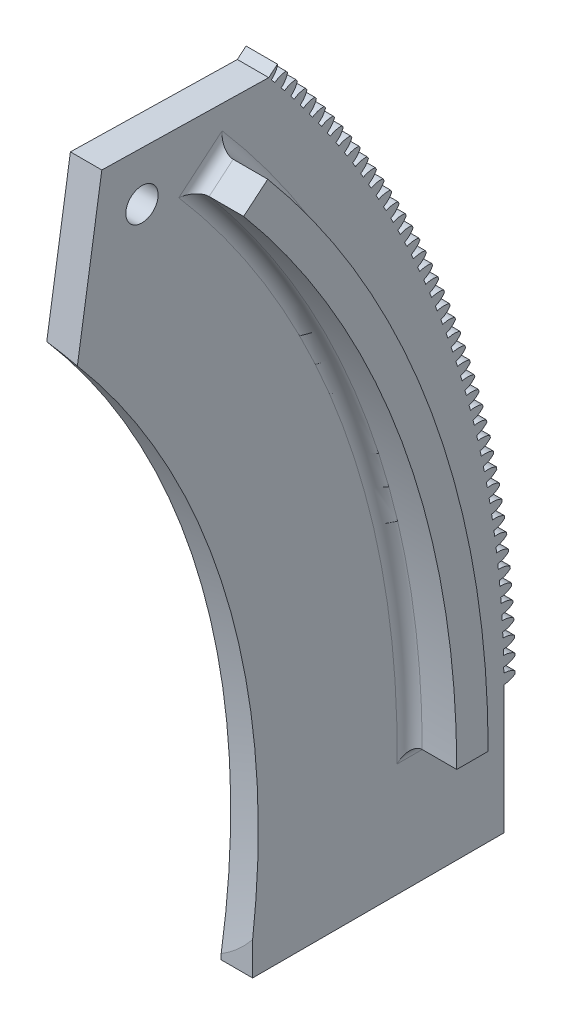
SolidWorks part; units mm, degrees
material "ABS"
ref_plane "Front Plane" through (0, 0, 0) normal (0, 0, 1) x (1, 0, 0)
ref_plane "Top Plane" through (0, 0, 0) normal (0, 1, 0) x (1, 0, 0)
ref_plane "Right Plane" through (0, 0, 0) normal (1, 0, 0) x (0, 0, -1)
ref_plane "Plane2" through (6.35, 0, 0) normal (1, 0, 0) x (0, 0, -1)
sketch "Sketch1" plane through (0, 0, 0) normal (1, 0, 0) x (0, 0, -1)
  line L0 (-1000, 0) -> (152.4, 0) construction
  line L1 (152.4, 0) -> (152.4, -25.4)
  line L2 (0, 0) -> (116.7452, 97.9608) construction
  line L4 (203.2, 0) -> (49000, 0) construction
  line L7 (152.4, -25.4) -> (203.2, -25.4)
  line L8 (203.2, 0) -> (203.2, -25.4)
  line L10 (-19.9245, -15.6845) -> (159.6649, 125.6875) construction
  line L61 (160.8976, 124.1056) -> (0, 0) construction
  line L62 (136.2027, 114.2876) -> (121.9167, 131.313) construction
  line L63 (116.7452, 97.9608) -> (121.9167, 131.313)
  line L67 (121.9167, 131.313) -> (155.6602, 130.6144)
  line L68 (0, 0) -> (35966.99, 34732.9185) construction
  line L69 (159.6736, 125.6943) -> (159.6985, 125.714) construction
  arc A2 (152.4, 0) -> (116.7452, 97.9608) centre (0, 0) ccw
  circle A19 centre (0, 0) radius 203.2 construction
  arc A22 (155.6602, 130.6144) -> (203.2, 0) centre (0, 0) cw
  point P6 (159.6985, 125.714)
  point P7 (116.7452, 97.9608)
  dimension "D1" = 152.4
  dimension "D2" = 6.35
  dimension "D12" = 406.4
  dimension "D3" = 40
  dimension "D4" = 50.8
  dimension "D5" = 25.4
  dimension "D11" = 22.225
  dimension "D13" = 44
sketch "Sketch2" plane through (6.35, 0, 0) normal (1, 0, 0) x (0, 0, -1)
  line L0 (0, 0) -> (165.1, 0) construction
  line L1 (165.1, 0) -> (190.5, 0) construction
  line L2 (0, 0) -> (49240.3877, 8682.4089) construction
  circle A0 centre (165.1, 0) radius 3.2639
  circle A1 centre (190.5, 0) radius 3.2639
  arc A3 (165.1, 0) -> (162.5918, 28.6693) centre (0, 0) ccw construction
  circle A4 centre (162.5918, 28.6693) radius 3.2639
  arc A5 (190.5, 0) -> (187.6059, 33.08) centre (0, 0) ccw construction
  circle A6 centre (187.6059, 33.08) radius 3.2639
  dimension "D3" = 6.5278
  dimension "D4" = 6.5278
  dimension "D6" = 6.5278
  dimension "D7" = 6.5278
  dimension "D1" = 165.1
  dimension "D2" = 25.4
  dimension "D5" = 10
sketch "Sketch11" plane through (6.35, 0, 0) normal (1, 0, 0) x (0, 0, -1)
  line L0 (-785.502, -659.1144) -> (0, 0) construction
  line L2 (-1000, 0) -> (0, 0) construction
  line L3 (203.2, 0) -> (205.5, 0)
  line L4 (155.6602, 130.6144) -> (157.4221, 132.0929)
  line L5 (157.4221, 132.0929) -> (921.7047, 773.4021) construction
  arc A0 (-230, 0) -> (-176.1902, -147.8412) centre (0, 0) ccw construction
  arc A1 (-205.5, 0) -> (-157.4221, -132.0929) centre (0, 0) ccw construction
  arc A2 (-203.1, 0) -> (-155.5836, -130.5502) centre (0, 0) ccw construction
  arc A3 (205.5, 0) -> (157.4221, 132.0929) centre (0, 0) ccw
  arc A4 (230, 0) -> (176.1902, 147.8412) centre (0, 0) ccw construction
  arc A5 (-203.1, 0) -> (-155.5836, -130.5502) centre (0, 0) ccw
  arc A6 (155.6602, 130.6144) -> (203.2, 0) centre (0, 0) cw
  dimension "D1" = 460
  dimension "D2" = 411
  dimension "D4" = 203.2
  dimension "D3" = 2.4
  dimension "D5" = 40
extrude "Boss-Extrude2" add sketch "Sketch11" against normal blind 6.35 contours L3 A3 L4 region at (6.35, 69.9814, -192.2722)
sketch "Sketch12" plane through (6.35, 0, 0) normal (1, 0, 0) x (0, 0, -1)
  line L0 (0, 0) -> (205.5, 0) construction
  line L1 (203.2, 0) -> (205.5, 0) construction
  line L2 (204.4985, 0.7854) -> (204.4985, -0.7854) construction
  line L3 (0, 0) -> (203.1992, 0.5545) construction
  line L4 (202.3406, 0) -> (206.4945, 1.5119) construction
  line L5 (0, 0) -> (206.4939, 1.5861) construction
  line L6 (204.4985, 0.7854) -> (204.4864, 2.3561) construction
  circle A0 centre (0, 0) radius 204.5 construction
  arc A1 (205.5, 0) -> (157.4221, 132.0929) centre (0, 0) ccw construction
  circle A2 centre (0, 0) radius 203.2 construction
  arc A3 (203.1992, 0.5545) -> (206.4856, 2.4358) centre (203.1888, 4.3838) ccw
  arc A4 (206.5, 0) -> (206.4856, -2.4358) centre (0, 0) cw
  arc A5 (203.1992, -0.5545) -> (206.4856, -2.4358) centre (203.1888, -4.3838) cw
  arc A6 (206.5, 0) -> (158.1882, 132.7356) centre (0, 0) ccw
  arc A7 (206.5, 0) -> (206.4856, 2.4358) centre (0, 0) ccw
  arc A8 (203.1992, 0.5545) -> (203.1992, -0.5545) centre (0, 0) cw
  dimension "D1" = 409
  dimension "D5" = 406.4
  dimension "D3" = 20
  dimension "D4" = 0.44
  dimension "D2" = 1
extrude "Boss-Extrude3" add sketch "Sketch1" along normal blind 6.35
extrude "Cut-Extrude4" cut sketch "Sketch12" against normal blind 6.35
pattern_circular "CirPattern3" count 100 every 0.88 about axis through (0, 0, 0) along (1, 0, 0) of "Cut-Extrude4"
sketch "Sketch15" plane through (6.35, 0, 0) normal (1, 0, 0) x (0, 0, -1)
  line L0 (0, 0) -> (130.0347, 121.2593) construction
  line L1 (-196961.5506, -34729.6355) -> (246201.9383, 43412.0444) construction
  circle A0 centre (130.0347, 121.2593) radius 3.2639
  dimension "D3" = 6.5278
  dimension "D1" = 177.8
  dimension "D2" = 33
extrude "Cut-Extrude7" cut sketch "Sketch15" against normal through all
sketch "Sketch21" plane through (0, 0, 0) normal (0, 1, 0) x (1, 0, 0)
  line L0 (0, 0) -> (-11.1125, 0) construction
  line L1 (12.7, 0) -> (12.7, 152.4)
  line L2 (0, 0) -> (12.7, 0) construction
  line L3 (-11.1125, 0) -> (-11.1125, 38.1) construction
  line L4 (-11.1125, 38.1) -> (-127.8666, 38.1)
  line L5 (-11.1125, 38.1) -> (105.6416, 38.1)
  line L6 (107.5153, 38.1) -> (-49892.4847, 38.1) construction
  line L7 (-1000, 0) -> (49000, 0) construction
  arc A0 (105.6416, 38.1) -> (-127.8666, 38.1) centre (-11.1125, 38.1) ccw
  dimension "D3" = 12.7
  dimension "D1" = 11.1125
  dimension "D2" = 152.4
  dimension "D4" = 38.1
revolve "Cut-Revolve7" cut sketch "Sketch21" angle 360 about L7 reverse direction yes
sketch "Sketch22" plane through (6.35, 0, 0) normal (1, 0, 0) x (0, 0, -1)
  line L0 (0, 0) -> (130.0347, 121.2593)
  line L1 (0, 0) -> (177.8, 0)
  dimension "D1" = 177.8
sketch "Sketch23" plane through (6.35, 0, 0) normal (1, 0, 0) x (0, 0, -1)
  line L0 (0, 0) -> (152.4, 0) construction
  line L1 (0, 0) -> (116.7452, 97.9608) construction
  line L2 (152.4, 0) -> (177.8, 0) construction
  line L3 (116.7452, 97.9608) -> (141.0671, 118.3693) construction
  line L4 (184.15, 0) -> (190.5, 0)
  line L5 (141.0671, 118.3693) -> (145.9315, 122.451)
  arc A0 (152.4, 0) -> (116.7452, 97.9608) centre (0, 0) ccw construction
  circle A2 centre (177.8, 0) radius 6.35 construction
  arc A3 (184.15, 0) -> (141.0671, 118.3693) centre (0, 0) ccw
  arc A4 (190.5, 0) -> (145.9315, 122.451) centre (0, 0) ccw
  circle A5 centre (196.85, 0) radius 6.35 construction
  dimension "D4" = 6.35
  dimension "D5" = 12.7
  dimension "D6" = 12.7
  dimension "D1" = 152.4
  dimension "D2" = 40
  dimension "D3" = 25.4
extrude "Boss-Extrude4" add sketch "Sketch23" along normal blind 9.525
fillet "Fillet1" radius 2.54 1 edges at (6.35, 62.983, -173.0444)
fillet "Fillet2" radius 2.54 1 edges at (6.35, 65.1548, -179.0114)
fillet "Fillet3" radius 2.54 1 edges at (6.35, 120.4102, -143.4993)
fillet "Fillet4" radius 2.54 1 edges at (6.35, 0, -187.325)
equation "\"Module\"= 1mm"
equation "\"Number of Teeth\"= 409"
equation "\"D1@Sketch12\"=\"Module\" * \"Number of Teeth\""
equation "\"D4@Sketch12\"=180 / \"Number of Teeth\""
equation "\"D2\"= 360 / \"Number of Teeth\""
equation "\"D2@Sketch11\"=( \"Number of Teeth\" + 2) * \"Module\""
equation "\"D2@CirPattern3\"= 360 / \"Number of Teeth\""
